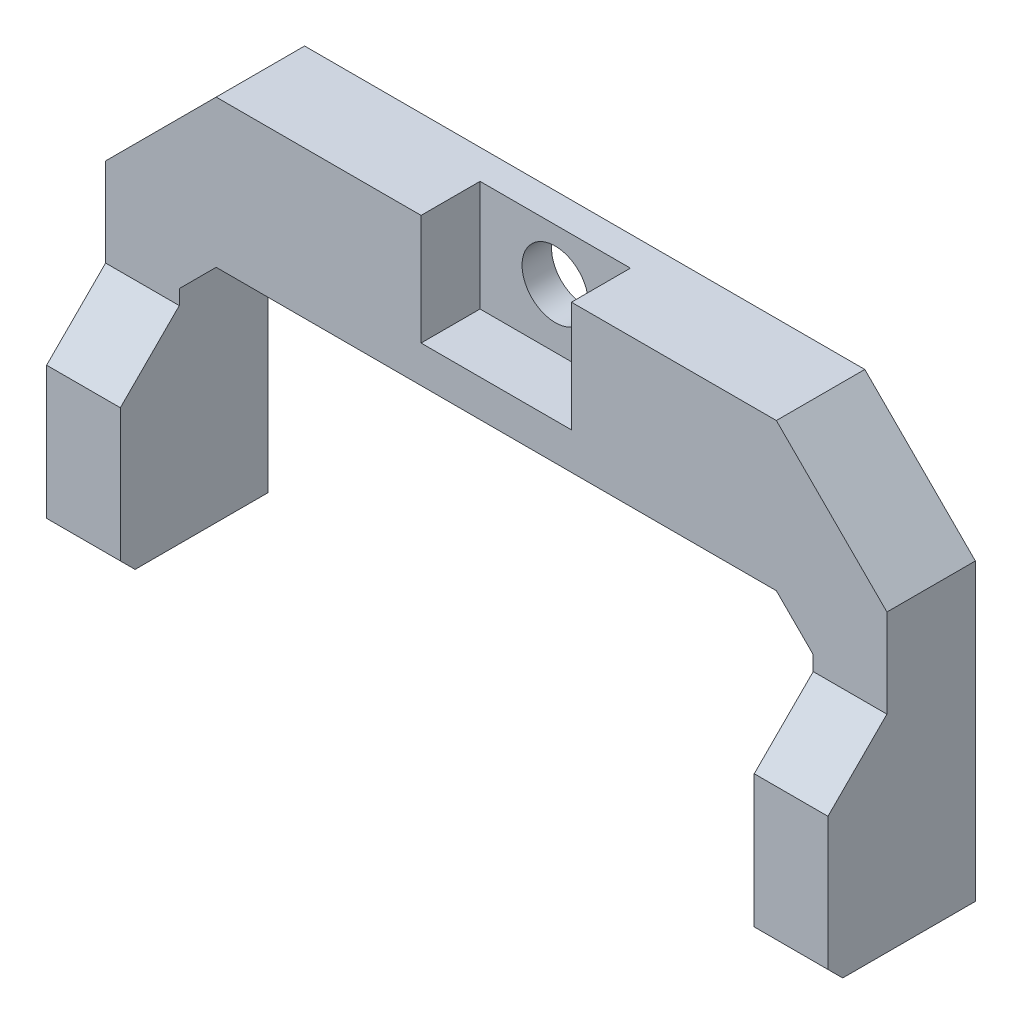
SolidWorks part; units mm, degrees
ref_plane "Front Plane" through (0, 0, 0) normal (0, 0, 1) x (1, 0, 0)
ref_plane "Top Plane" through (0, 0, 0) normal (0, 1, 0) x (1, 0, 0)
ref_plane "Right Plane" through (0, 0, 0) normal (1, 0, 0) x (0, 0, -1)
sketch "Sketch1" plane through (0, 0, 0) normal (0, 0, 1) x (1, 0, 0)
  line L0 (0, 0) -> (0, -10)
  line L1 (0, -10) -> (-19, -10)
  line L2 (-19, -10) -> (-21.5, -12.5)
  line L3 (-21.5, -12.5) -> (-21.5, -27.5)
  line L4 (-21.5, -27.5) -> (-26.5, -27.5)
  line L5 (-26.5, -27.5) -> (-26.5, -7.5)
  line L6 (-26.5, -7.5) -> (-19, 0)
  line L7 (-19, 0) -> (0, 0)
  dimension "D1" = 135
  dimension "D2" = 21.5
  dimension "D3" = 5
  dimension "D4" = 15
  dimension "D5" = 10
  dimension "D6" = 2.5
extrude "Boss-Extrude1" add sketch "Sketch1" along normal blind 6
sketch "Sketch6" plane through (0, 0, 6) normal (0, 0, 1) x (1, 0, 0)
  line L0 (-21.5, -27.5) -> (-21.5, -12.5) construction
  line L1 (-26.5, -27.5) -> (-21.5, -27.5)
  line L2 (-26.5, -27.5) -> (-26.5, -17.5)
  line L3 (-26.5, -17.5) -> (-21.5, -17.5)
  line L4 (-21.5, -27.5) -> (-21.5, -17.5)
  dimension "D1" = 10
extrude "Boss-Extrude2" add sketch "Sketch6" along normal blind 4
sketch "Sketch3" plane through (0, 0, 6) normal (0, 0, 1) x (1, 0, 0)
  line L1 (0, 0) -> (-5.1, 0)
  line L2 (0, 0) -> (0, -7.5)
  line L3 (0, -7.5) -> (-5.1, -7.5)
  line L4 (-5.1, 0) -> (-5.1, -7.5)
  dimension "D1" = 7.5
  dimension "D2" = 5.1
extrude "Cut-Extrude1" cut sketch "Sketch3" against normal blind 4
mirror "Mirror1" about plane through (0, 0, 6) normal (-1, 0, 0) of "Boss-Extrude2", "Boss-Extrude1", "Cut-Extrude1"
hole_wizard "M4 Clearance Hole1" positions "Sketch4" profile "Sketch5" hole size "M4" standard "ANSI Metric" end condition through all
sketch "Sketch4" plane through (0, 0, 2) normal (0, 0, 1) x (1, 0, 0)
  line L0 (-5.1, -7.5) -> (5.1, -7.5) construction
  line L1 (0, -55) -> (0, 55) construction
  point P0 (0, -3.5)
  dimension "D1" = 4
sketch "Sketch5" plane through (0, -3.5, 2) normal (1, 0, 0) x (0, -1, 0)
  line L0 (0, 0) -> (0, 2)
  line L1 (0, 2) -> (2.25, 2)
  line L2 (2.25, 2) -> (2.25, 0)
  line L5 (2.25, 0) -> (0, 0)
  line L11 (0, -6.35) -> (0, 107.95) construction
  dimension "Thru Hole Dia." = 4.5
  dimension "Thru Hole Depth" = 2
chamfer "Chamfer2" distance 4 2 edges at (24, -17.5, 6) (-24, -17.5, 6)
chamfer "Chamfer3" distance 1 angle 45 2 edges at (24, -27.5, 10) (-24, -27.5, 10)
equation "\"a\"=1"
